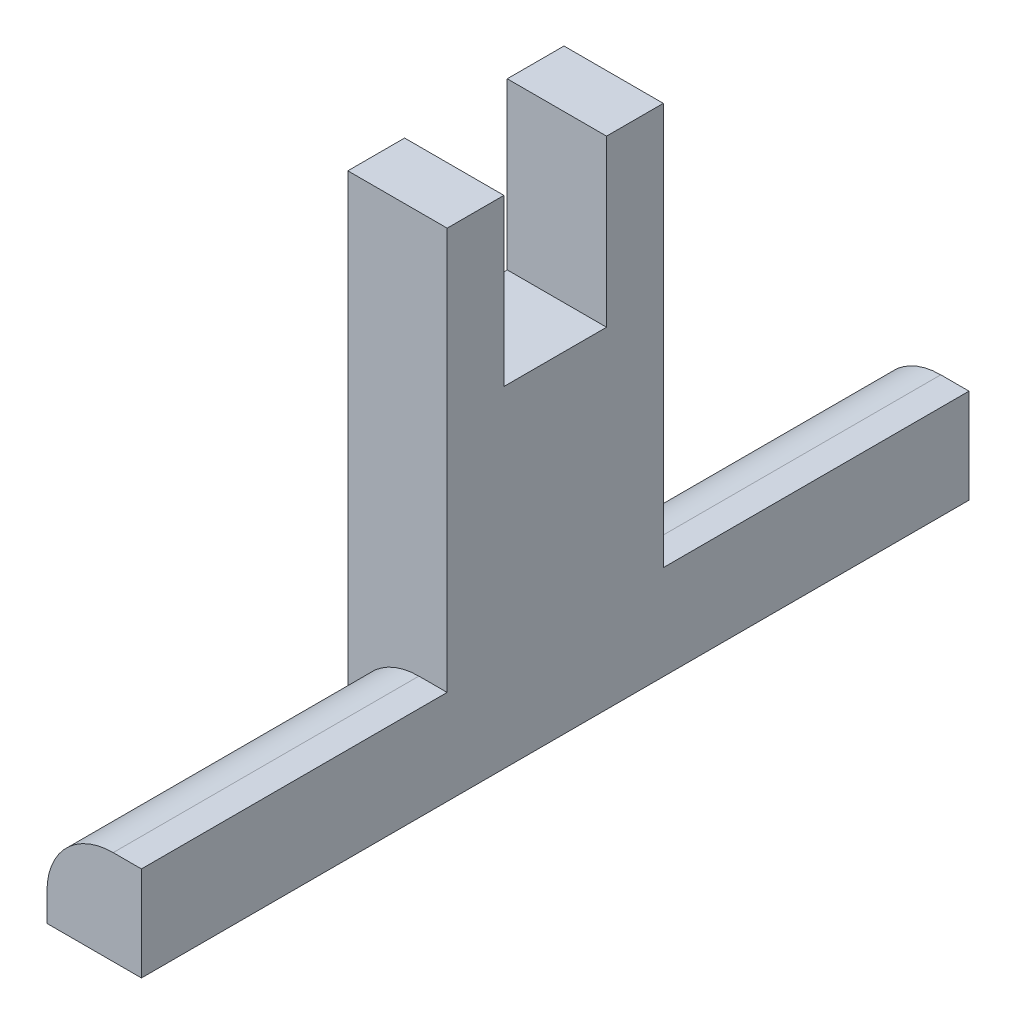
SolidWorks part; units mm, degrees
ref_plane "Front Plane" through (0, 0, 0) normal (0, 0, 1) x (1, 0, 0)
ref_plane "Top Plane" through (0, 0, 0) normal (0, 1, 0) x (1, 0, 0)
ref_plane "Right Plane" through (0, 0, 0) normal (1, 0, 0) x (0, 0, -1)
sketch "Sketch1" plane through (0, 0, 0) normal (1, 0, 0) x (0, 0, -1)
  line L0 (-3.1, 10) -> (-3.1, 0)
  line L1 (-3.1, 0) -> (-6.5301, 0)
  line L2 (-6.5301, 0) -> (-6.5301, 10)
  line L3 (-6.5301, 0) -> (-6.5301, -20)
  line L4 (-6.5301, -20) -> (6.5301, -20)
  line L5 (0, 0) -> (0, 50000) construction
  line L6 (6.5301, -20) -> (6.5301, 0)
  line L8 (6.5301, 0) -> (6.5301, 10)
  line L9 (3.1, 0) -> (6.5301, 0)
  line L10 (3.1, 10) -> (3.1, 0)
  line L11 (-3.1, 10) -> (3.1, 10)
  line L25 (6.5301, 10) -> (6.5301, 0.9112)
  line L26 (-6.5301, 10) -> (-6.5301, 0.9112)
  line L27 (-6.5301, 10) -> (-3.1, 10)
  line L28 (3.1, 10) -> (6.5301, 10)
  line L29 (3.1, 0) -> (-3.1, 0)
  line L35 (-25, 12.1535) -> (-25, -1.9655) construction
  line L36 (25, 12.1535) -> (25, -1.9655) construction
  dimension "D3" = 20
  dimension "D1" = 6.2
  dimension "D2" = 10
  dimension "D4" = 25
extrude "Boss-Extrude2" add sketch "Sketch1" against normal blind 6 contours L28 L10 L9 L8 | L27 L2 L1 L0 | L25 L26 L27 L11 L28 | L9 L29 L1 L3 L4 L6 region at (0, 5, 4.8151) region at (0, -10, 0) region at (0, 5, -4.8151)
sketch "Sketch2" plane through (0, 0, 6.5301) normal (0, 0, 1) x (1, 0, 0)
  line L1 (0, -20) -> (-5.7072, -20)
  line L2 (0, -20) -> (0, -14.2928)
  line L3 (0, -14.2928) -> (-1.7072, -14.2928)
  line L4 (-5.7072, -20) -> (-5.7072, -18.2928)
  arc A0 (-5.7072, -18.2928) -> (-1.7072, -14.2928) centre (-1.7072, -18.2928) cw
  dimension "D1" = 4
  dimension "D2" = 5.7072
extrude "Boss-Extrude3" add sketch "Sketch2" along normal up to vertex (18.4699 mm away) and the other way up to vertex (31.5301 mm away) up to point (0, -1.9655, 25) other way up to point (0, -1.9655, -25)
